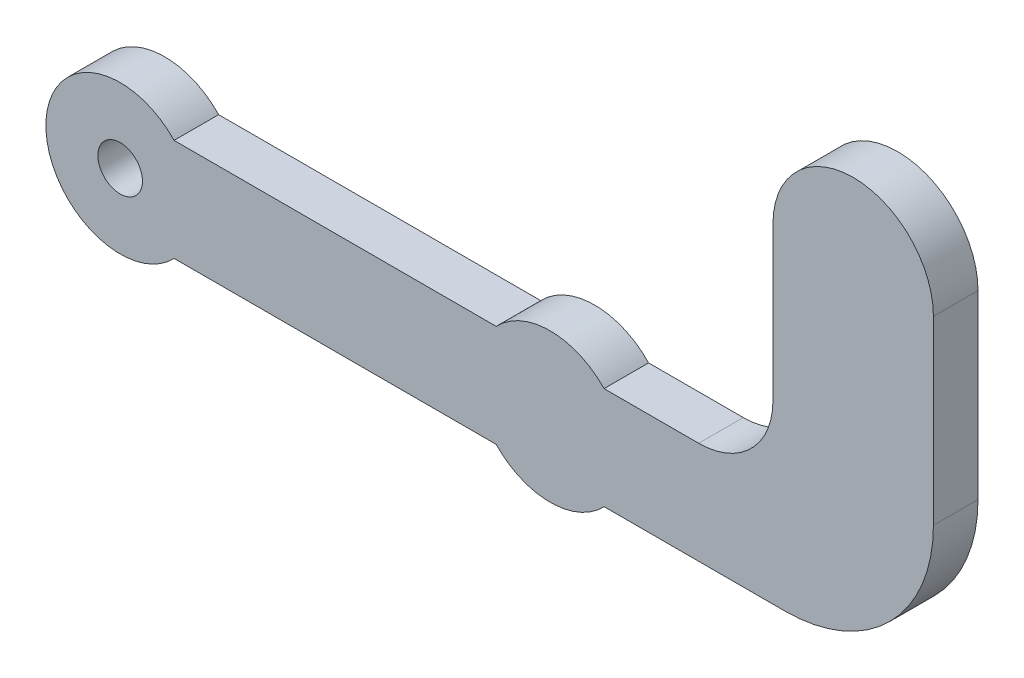
SolidWorks part; units mm, degrees
ref_plane "Alzado" through (0, 0, 0) normal (0, 0, 1) x (1, 0, 0)
ref_plane "Planta" through (0, 0, 0) normal (0, 1, 0) x (1, 0, 0)
ref_plane "Vista lateral" through (0, 0, 0) normal (1, 0, 0) x (0, 0, -1)
sketch "Croquis1" plane through (0, 0, 0) normal (0, 0, 1) x (1, 0, 0)
  line L3 (44.9959, 19.6999) -> (44.9959, -8.9601) construction
  line L6 (55.7959, -10.8401) -> (55.7959, 1.3399) construction
  line L8 (39.9959, -13.9601) -> (33.6245, -13.9601)
  line L10 (4.6845, -20.8401) -> (26.3674, -20.8401)
  line L12 (4.6845, -20.8401) -> (26.3674, -20.8401) construction
  line L13 (26.3674, -13.9601) -> (4.6845, -13.9601) construction
  line L15 (33.6245, -20.8401) -> (45.7959, -20.8401)
  line L16 (26.3674, -13.9601) -> (4.6845, -13.9601)
  line L17 (44.9959, -8.9601) -> (44.9959, 1.3399)
  line L19 (55.7959, -10.8401) -> (55.7959, 1.3399)
  arc A0 (33.6245, -13.9601) -> (26.3674, -13.9601) centre (29.9959, -17.4001) ccw
  arc A1 (4.6845, -13.9601) -> (4.6845, -20.8401) centre (1.0559, -17.4001) ccw
  circle A2 centre (50.3959, -9.1401) radius 1.5
  circle A3 centre (50.3959, 1.3399) radius 1.5
  circle A5 centre (29.9959, -17.4001) radius 1.5
  circle A6 centre (1.0559, -17.4001) radius 1.5
  arc A7 (26.3674, -20.8401) -> (33.6245, -20.8401) centre (29.9959, -17.4001) ccw
  arc A9 (44.9959, -8.9601) -> (39.9959, -13.9601) centre (39.9959, -8.9601) cw
  circle A13 centre (1.0559, -17.4001) radius 5 construction
  arc A14 (45.7959, -20.8401) -> (55.7959, -10.8401) centre (45.7959, -10.8401) ccw
  arc A15 (33.6245, -13.9601) -> (26.3674, -13.9601) centre (29.9959, -17.4001) ccw construction
  arc A16 (44.9959, 1.3399) -> (55.7959, 1.3399) centre (50.3959, 1.3399) cw
  point P9 (0, 0)
  point P21 (51.1554, -9.3699)
  point P36 (0, 0)
  point P39 (29.9959, -17.4001)
  point P45 (1.0559, -17.4001)
  point P47 (44.9959, -9.1401)
  point P48 (29.9959, -17.4001)
  dimension "D1" = 3
  dimension "D2" = 5
  dimension "D3" = 10
extrude "Saliente-Extruir1" add sketch "Croquis1" along normal blind 3
sketch "Croquis2" plane through (0, 0, 3) normal (0, 0, 1) x (1, 0, 0)
  circle A0 centre (50.3959, 1.3399) radius 1.5
  circle A1 centre (50.3959, -9.1401) radius 1.5
  circle A2 centre (29.9959, -17.4001) radius 1.5
  dimension "D1" = 3
extrude "Saliente-Extruir2" add sketch "Croquis2" against normal blind 1
sketch "Croquis3" plane through (0, 0, 0) normal (0, 0, -1) x (-1, 0, 0)
  circle A0 centre (-50.3959, -9.1401) radius 1.5
  circle A1 centre (-50.3959, -9.1401) radius 3
  circle A2 centre (-50.3959, 1.3399) radius 1.5
  circle A3 centre (-50.3959, 1.3399) radius 3
  circle A4 centre (-29.9959, -17.4001) radius 3
  circle A5 centre (-29.9959, -17.4001) radius 1.5
  dimension "D1" = 3
  dimension "D2" = 6
extrude "Saliente-Extruir3" add sketch "Croquis3" along normal up to surface (1.35 mm away)
chamfer "Chaflán1" distance 0.5 angle 45 3 edges at (47.3959, -9.1401, 0) (47.3959, 1.3399, 0) (26.9959, -17.4001, 0)
